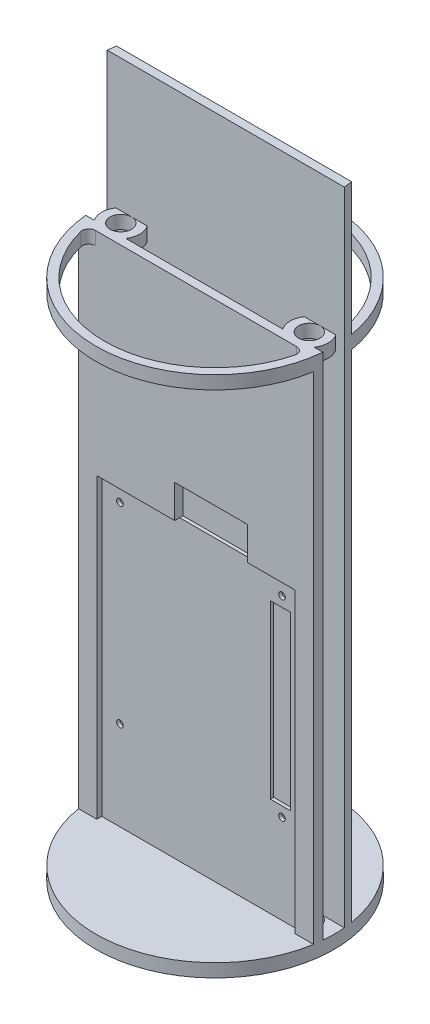
SolidWorks part; units mm, degrees
ref_plane "Front Plane" through (0, 0, 0) normal (0, 0, 1) x (1, 0, 0)
ref_plane "Top Plane" through (0, 0, 0) normal (0, 1, 0) x (1, 0, 0)
ref_plane "Right Plane" through (0, 0, 0) normal (1, 0, 0) x (0, 0, -1)
sketch "Sketch1" plane through (0, 0, 0) normal (0, 1, 0) x (1, 0, 0)
  circle A0 centre (0, 0) radius 36
  dimension "D1" = 72
extrude "Boss-Extrude1" add sketch "Sketch1" along normal blind 4
sketch "Sketch2" plane through (0, 4, 0) normal (0, 1, 0) x (1, 0, 0)
  line L0 (-36.3097, 0) -> (36, 0) construction
  line L1 (35.5378, -5.75) -> (-35.5378, -5.75)
  line L2 (35.5378, -5.75) -> (35.5378, 5.75)
  line L3 (35.5378, 5.75) -> (-35.5378, 5.75)
  line L4 (-35.5378, -5.75) -> (-35.5378, 5.75)
  line L5 (35.5378, -5.75) -> (-35.5378, 5.75) construction
  line L6 (35.5378, 5.75) -> (-35.5378, -5.75) construction
  line L7 (35.853, -3.25) -> (-35.853, -3.25)
  line L8 (35.853, -3.25) -> (35.853, 3.25)
  line L9 (35.853, 3.25) -> (-35.853, 3.25)
  line L10 (-35.853, -3.25) -> (-35.853, 3.25)
  line L11 (35.853, -3.25) -> (-35.853, 3.25) construction
  line L12 (35.853, 3.25) -> (-35.853, -3.25) construction
  circle A0 centre (-28.5, 0) radius 3.25
  circle A1 centre (0, 0) radius 36
  circle A2 centre (0, 0) radius 36
  circle A3 centre (28.5, 0) radius 3.25
  circle A4 centre (-28.5, 0) radius 5.75
  circle A5 centre (28.5, 0) radius 5.75
  circle M4 centre (0, 0) radius 36
  dimension "D5" = 28.5
  dimension "D2" = 11.5
  dimension "D3" = 6.5
  dimension "D4" = 57
  dimension "D1" = 0
extrude "Boss-Extrude2" add sketch "Sketch2" along normal blind 90 contours L9 A4 | A4 L3 L4 L9 | A5 L3 A4 L9 | L9 A5 | A5 L9 L2 L3 | A5 L1 L2 L7 | A5 L7 | A5 L7 A4 L1 | A4 L7 | A4 L7 L4 L1 | L9 L4 M4 | L4 L7 M4 | L9 L2 M4 | L7 L2 M4 region at (33.5238, 4, 4.7055) region at (35.6482, 4, 4.1192) region at (0, 4, 4.5303) region at (28.5, 4, 4.2713) region at (-33.5238, 4, 4.7055) region at (-35.6482, 4, 4.1192) region at (-28.5, 4, 4.2713) region at (33.5238, 4, -4.7055) region at (35.6482, 4, -4.1192) region at (28.5, 4, -4.2713) region at (0, 4, -4.5303) region at (-35.6482, 4, -4.1192) region at (-33.5238, 4, -4.7055) region at (-28.5, 4, -4.2713)
sketch "Sketch4" plane through (0, 4, 0) normal (0, 1, 0) x (1, 0, 0)
  circle A0 centre (-28.5, 0) radius 3.25
  circle A1 centre (28.5, 0) radius 3.25
  dimension "D1" = 6.5
  dimension "D2" = 6.5
  dimension "D3" = 57
  dimension "D4" = 28.5
extrude "Cut-Extrude2" cut sketch "Sketch4" against normal blind 10
sketch "Sketch3" plane through (0, 94, 0) normal (0, 1, 0) x (1, 0, 0)
  line L0 (35.5378, -5.75) -> (-35.5378, -5.75) construction
  line L1 (-30, -5.75) -> (30, -5.75)
  line L2 (-30, -5.75) -> (-30, -4.25)
  line L3 (-30, -4.25) -> (30, -4.25)
  line L4 (30, -5.75) -> (30, -4.25)
  point P6 (-30, -5)
  dimension "D1" = 1.5
  dimension "D2" = 30
  dimension "D3" = 60
extrude "Cut-Extrude1" cut sketch "Sketch3" against normal blind 90
sketch "Sketch6" plane through (0, 0, 4.25) normal (0, 0, 1) x (1, 0, 0)
  line L0 (30, 4) -> (30, 94) construction
  line L1 (27, 86) -> (21, 86)
  line L2 (27, 86) -> (27, 34)
  line L3 (27, 34) -> (21, 34)
  line L4 (21, 86) -> (21, 34)
  line L5 (30, 94) -> (-30, 94) construction
  dimension "D1" = 6
  dimension "D2" = 3
  dimension "D3" = 8
  dimension "D4" = 52
extrude "Cut-Extrude4" cut sketch "Sketch6" against normal blind 5
sketch "Sketch7" plane through (0, 0, 4.25) normal (0, 0, 1) x (1, 0, 0)
  line L0 (30, 94) -> (-30, 94) construction
  line L1 (-30, 4) -> (-30, 94) construction
  circle A0 centre (-24.5, 89) radius 1
  circle A1 centre (24.5, 89) radius 1
  circle A2 centre (24.5, 31) radius 1
  circle A3 centre (-24.5, 31) radius 1
  dimension "D1" = 2
  dimension "D2" = 5
  dimension "D5" = 5.5
  dimension "D3" = 2
  dimension "D4" = 2
extrude "Cut-Extrude5" cut sketch "Sketch7" against normal blind 5 contours A1 | A2 | A3 | A0 region at (24.5, 89, 4.25) region at (24.5, 31, 4.25) region at (-24.5, 31, 4.25)
sketch "Sketch8" plane through (0, 0, -5.75) normal (0, 0, -1) x (-1, 0, 0)
  line L0 (-35.5378, 94) -> (-35.5378, 4) construction
  line L1 (-26.5378, 29) -> (17.4622, 29)
  line L2 (-26.5378, 29) -> (-26.5378, 117)
  line L3 (-26.5378, 117) -> (17.4622, 117)
  line L4 (17.4622, 29) -> (17.4622, 117)
  line L5 (-26.5378, 29) -> (17.4622, 117) construction
  line L6 (-26.5378, 117) -> (17.4622, 29) construction
  line L7 (-35.5378, 4) -> (35.5378, 4) construction
  circle A0 centre (-26.5378, 117) radius 1.5
  circle A1 centre (17.4622, 117) radius 1.5
  circle A2 centre (17.4622, 29) radius 1.5
  circle A3 centre (-26.5378, 29) radius 1.5
  point P3 (-4.5378, 73)
  dimension "D1" = 3
  dimension "D5" = 25
  dimension "D4" = 9
  dimension "D2" = 2
  dimension "D3" = 2
sketch "Sketch9" plane through (0, 94, 0) normal (0, 1, 0) x (1, 0, 0)
  line L0 (35.853, 3.25) -> (-35.853, 3.25) construction
  line L1 (-28.5, 3.25) -> (-35.853, 3.25) construction
  line L2 (35.5378, 5.75) -> (-35.5378, 5.75) construction
  line L3 (35.853, 3.25) -> (-35.853, 3.25)
  line L4 (-28.5, 3.25) -> (-35.853, 3.25)
  line L5 (35.5378, 5.75) -> (-35.5378, 5.75)
  line L6 (-30, -5.75) -> (-30, -4.25)
  line L7 (-30, -4.25) -> (30, -4.25)
  line L8 (30, -4.25) -> (30, -5.75)
  line L9 (30, -5.75) -> (35.5378, -5.75)
  line L10 (35.853, -3.25) -> (-35.853, -3.25)
  line L11 (-35.5378, -5.75) -> (-30, -5.75)
  line L15 (30, -5.75) -> (35.5378, -5.75)
  line L16 (35.853, -3.25) -> (-35.853, -3.25)
  line L17 (-35.5378, -5.75) -> (-30, -5.75)
  line L18 (-30, -5.75) -> (30, -5.75)
  arc A0 (-35.5378, 5.75) -> (-35.853, 3.25) centre (0, 0) ccw construction
  arc A1 (35.853, 3.25) -> (35.5378, 5.75) centre (0, 0) ccw construction
  arc A2 (35.5378, -5.75) -> (35.853, -3.25) centre (0, 0) ccw
  arc A3 (-35.853, -3.25) -> (-35.5378, -5.75) centre (0, 0) ccw
  arc A4 (35.5378, -5.75) -> (35.853, -3.25) centre (0, 0) ccw
  arc A5 (-35.853, -3.25) -> (-35.5378, -5.75) centre (0, 0) ccw
  arc A6 (-35.5378, 5.75) -> (-35.853, 3.25) centre (0, 0) ccw
  arc A7 (35.853, 3.25) -> (35.5378, 5.75) centre (0, 0) ccw
  line M9 (-30, -5.75) -> (-30, -4.25)
  line M10 (-30, -4.25) -> (30, -4.25)
  line M11 (30, -4.25) -> (30, -5.75)
  line M12 (30, -5.75) -> (35.5378, -5.75)
  arc M13 (35.5378, -5.75) -> (35.853, -3.25) centre (0, 0) ccw
  line M14 (35.853, -3.25) -> (-35.853, -3.25)
  arc M15 (-35.853, -3.25) -> (-35.5378, -5.75) centre (0, 0) ccw
  line M16 (-35.5378, -5.75) -> (-30, -5.75)
  dimension "D1" = 0
extrude "Boss-Extrude3" add sketch "Sketch9" along normal blind 60 contours L3 A7 L5 A6 | M16 M9 M10 M11 M12 M13 M14 M15 | L18 M9 M11 M10 region at (0, 94, -4.4982) region at (0, 94, 3.9881) region at (0, 94, 5)
sketch "Sketch10" plane through (0, 0, 5.75) normal (0, 0, 1) x (1, 0, 0)
  line L0 (30, 94) -> (-30, 94) construction
  line L1 (15.5378, 94) -> (-6.4622, 94)
  line L2 (15.5378, 94) -> (15.5378, 104)
  line L3 (15.5378, 104) -> (-6.4622, 104)
  line L4 (-6.4622, 94) -> (-6.4622, 104)
  line L5 (15.5378, 94) -> (-6.4622, 104) construction
  line L6 (15.5378, 104) -> (-6.4622, 94) construction
  point P4 (4.5378, 99)
  dimension "D1" = 22
  dimension "D2" = 10
extrude "Cut-Extrude6" cut sketch "Sketch10" against normal blind 5 contours L4 L3 L2 L1
extrude "Cut-Extrude7" cut sketch "Sketch8" against normal blind 5 contours A3 | A2 | A1 | A0
sketch "Sketch11" plane through (0, 154, 0) normal (0, 1, 0) x (1, 0, 0)
  line L5 (-35.5378, -5.75) -> (35.5378, -5.75) construction
  line L6 (-23.7566, 3.25) -> (23.7566, 3.25)
  line L7 (35.853, 3.25) -> (28.5, 3.25) construction
  line L8 (35.5378, 5.75) -> (-35.5378, 5.75) construction
  line L9 (35.853, -3.25) -> (-35.853, -3.25) construction
  line L10 (-28.5, 3.25) -> (-35.853, 3.25) construction
  line L11 (-35.853, -3.25) -> (-28.5, -3.25) construction
  line L12 (-35.853, 3.25) -> (35.853, 3.25) construction
  line L13 (-30.4305, -5.75) -> (30.4305, -5.75)
  line L14 (-28.5, -3.25) -> (28.5, -3.25) construction
  line L15 (28.5, 3.25) -> (-28.5, 3.25) construction
  line L18 (-33.2434, -3.25) -> (-35.853, -3.25)
  line L21 (30.4305, 5.75) -> (-30.4305, 5.75)
  line L23 (35.853, 3.25) -> (33.2434, 3.25)
  line L25 (35.853, -3.25) -> (28.5, -3.25)
  line L26 (-33.2434, 3.25) -> (-35.853, 3.25)
  line L27 (-35.853, -3.25) -> (-33.2434, -3.25)
  line L28 (-35.853, 3.25) -> (28.5, 3.25)
  line L30 (-23.7566, -3.25) -> (23.7566, -3.25)
  line L31 (28.5, 3.25) -> (-28.5, 3.25)
  line L32 (23.7566, -3.25) -> (-23.7566, -3.25)
  line L33 (33.2434, 3.25) -> (35.853, 3.25)
  arc A0 (-35.5378, -5.75) -> (35.5378, -5.75) centre (0, 0) ccw construction
  arc A1 (35.5378, 5.75) -> (-35.5378, 5.75) centre (0, 0) ccw construction
  arc A2 (28.5, -3.25) -> (28.5, 3.25) centre (28.5, 0) ccw construction
  arc A3 (35.853, -3.25) -> (35.853, 3.25) centre (0, 0) ccw construction
  arc A4 (35.5378, -5.75) -> (35.853, -3.25) centre (0, 0) ccw construction
  arc A5 (-35.853, -3.25) -> (-35.5378, -5.75) centre (0, 0) ccw construction
  arc A6 (-28.5, 3.25) -> (-28.5, -3.25) centre (-28.5, 0) ccw construction
  arc A7 (-35.853, 3.25) -> (-35.853, -3.25) centre (0, 0) ccw construction
  arc A8 (35.853, 3.25) -> (35.5378, 5.75) centre (0, 0) ccw construction
  arc A9 (-35.5378, 5.75) -> (-35.853, 3.25) centre (0, 0) ccw construction
  arc A10 (-28.5, -3.25) -> (-28.5, 3.25) centre (-28.5, 0) ccw construction
  arc A11 (28.5, 3.25) -> (28.5, -3.25) centre (28.5, 0) ccw construction
  arc A12 (-35.5378, -5.75) -> (35.5378, -5.75) centre (0, 0) ccw
  arc A13 (35.5378, 5.75) -> (-35.5378, 5.75) centre (0, 0) ccw
  arc A14 (28.5, -3.25) -> (28.5, 3.25) centre (28.5, 0) ccw
  arc A15 (35.853, -3.25) -> (35.853, 3.25) centre (0, 0) ccw
  arc A16 (35.5378, -5.75) -> (35.853, -3.25) centre (0, 0) ccw
  arc A17 (-35.853, -3.25) -> (-35.5378, -5.75) centre (0, 0) ccw
  arc A18 (-28.5, 3.25) -> (-28.5, -3.25) centre (-28.5, 0) ccw
  arc A19 (-35.853, 3.25) -> (-35.853, -3.25) centre (0, 0) ccw
  arc A20 (35.853, 3.25) -> (35.5378, 5.75) centre (0, 0) ccw
  arc A21 (-35.5378, 5.75) -> (-35.853, 3.25) centre (0, 0) ccw
  arc A22 (-28.5, -3.25) -> (-28.5, 3.25) centre (-28.5, 0) ccw
  arc A23 (28.5, 3.25) -> (28.5, -3.25) centre (28.5, 0) ccw
  arc A24 (-33.2434, 3.25) -> (-33.2434, -3.25) centre (-28.5, 0) ccw
  arc A25 (23.7566, 3.25) -> (23.7566, -3.25) centre (28.5, 0) ccw
  arc A28 (-23.7566, -3.25) -> (-23.7566, 3.25) centre (-28.5, 0) ccw
  arc A29 (-32.3687, -8.2436) -> (32.3687, -8.2436) centre (0, 0) ccw
  arc A30 (33.2434, -3.25) -> (33.2434, 3.25) centre (28.5, 0) ccw
  arc A32 (32.3687, 8.2436) -> (-32.3687, 8.2436) centre (0, 0) ccw
  arc A33 (30.4305, -5.75) -> (32.3687, -8.2436) centre (30.4305, -7.75) cw
  arc A34 (-30.4305, -5.75) -> (-32.3687, -8.2436) centre (-30.4305, -7.75) ccw
  arc A35 (-32.3687, 8.2436) -> (-30.4305, 5.75) centre (-30.4305, 7.75) ccw
  arc A36 (32.3687, 8.2436) -> (30.4305, 5.75) centre (30.4305, 7.75) cw
  line M1 (-35.853, 3.25) -> (35.853, 3.25)
  arc M2 (35.853, 3.25) -> (35.5378, 5.75) centre (0, 0) ccw
  line M3 (35.5378, 5.75) -> (-35.5378, 5.75)
  arc M4 (-35.5378, 5.75) -> (-35.853, 3.25) centre (0, 0) ccw
  dimension "D1" = 2
  dimension "D2" = 2
  dimension "D3" = 2
extrude "Boss-Extrude4" add sketch "Sketch11" along normal blind 4 contours L28 M4 M1 M2 M3 | A32 A36 A13 A35 M3 | L30 A28 L28 A22 A18 A24 L18 A17 A12 A16 L25 A23 A25 A34 L13 A33 A29 M1 | L25 A30 A14 M1 region at (0, 154, -4.4982) region at (-23.5675, 154, 0) region at (32.4135, 154, 0) region at (0, 154, -35.2275)
sketch "Sketch12" plane through (0, 158, 0) normal (0, 1, 0) x (1, 0, 0)
  line L1 (-35.853, 3.25) -> (35.853, 3.25)
  line L3 (-35.5378, 5.75) -> (35.5378, 5.75)
  arc A0 (35.853, 3.25) -> (-35.853, 3.25) centre (0, 0) ccw construction
  arc A1 (35.853, 3.25) -> (35.5378, 5.75) centre (0, 0) ccw
  arc A2 (-35.5378, 5.75) -> (-35.853, 3.25) centre (0, 0) ccw
extrude "Boss-Extrude5" add sketch "Sketch12" along normal blind 40
